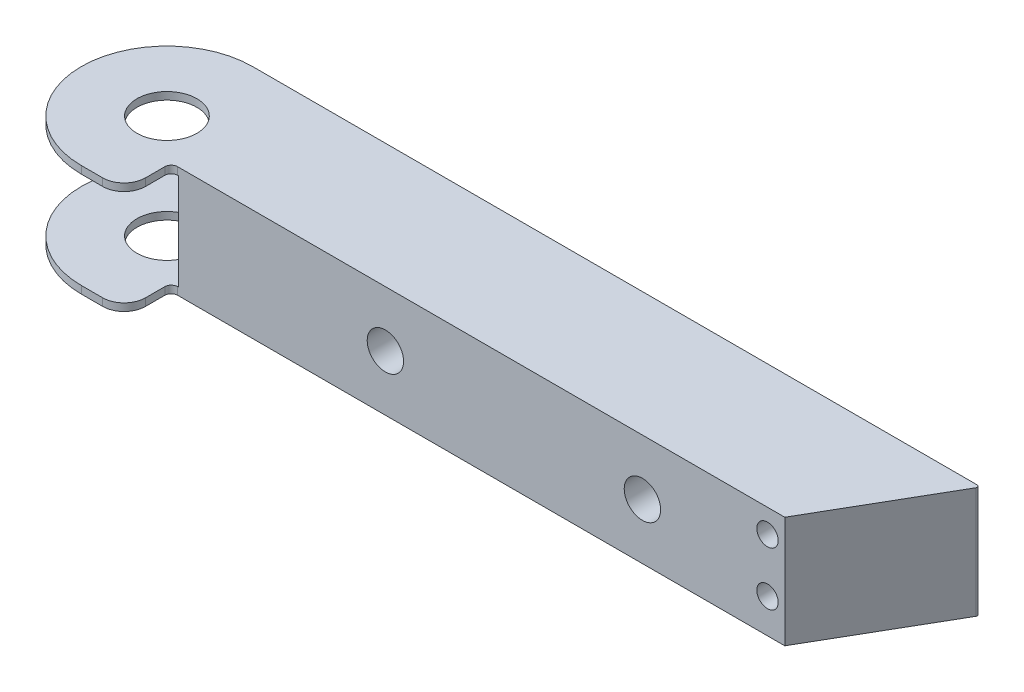
SolidWorks part; units mm, degrees
material "Nylon 6/10"
ref_plane "Front Plane" through (0, 0, 0) normal (0, 0, 1) x (1, 0, 0)
ref_plane "Top Plane" through (0, 0, 0) normal (0, 1, 0) x (1, 0, 0)
ref_plane "Right Plane" through (0, 0, 0) normal (1, 0, 0) x (0, 0, -1)
sketch "Sketch1" plane through (0, 0, 0) normal (0, 1, 0) x (1, 0, 0)
  line L0 (0, 0) -> (38, 0)
  line L1 (38, 0) -> (30, -8)
  line L2 (30, -8) -> (0, -8)
  line L3 (0, -8) -> (0, 0)
  dimension "D1" = 38
  dimension "D2" = 30
  dimension "D3" = 8
extrude "Boss-Extrude1" add sketch "Sketch1" along normal blind 5.5
sketch "Sketch3" plane through (0, 5.5, 0) normal (0, 1, 0) x (1, 0, 0)
  line L0 (2, 0) -> (2, -2) construction
  line L1 (38, 0) -> (0, 0) construction
  line L2 (2, -2) -> (0, -2) construction
  line L3 (0, 0) -> (0, -8) construction
  dimension "D1" = 2
  dimension "D2" = 2
sketch "Sketch4" plane through (0, 0, 8) normal (0, 0, 1) x (1, 0, 0)
  line L12 (0, 0.5) -> (6, 0.5)
  line L13 (0, 5.5) -> (0, 0) construction
  line L14 (6, 0.5) -> (6, 0)
  line L15 (0, 0) -> (30, 0) construction
  line L16 (6, 0) -> (38, 0)
  line L17 (38, 0) -> (38, 5.5)
  line L18 (38, 5.5) -> (6, 5.5)
  line L19 (0, 5.5) -> (30, 5.5) construction
  line L20 (6, 5.5) -> (6, 5)
  line L21 (6, 5) -> (0, 5)
  line L22 (0, 5) -> (0, 0.5)
  dimension "D1" = 6
  dimension "D2" = 6
  dimension "D3" = 0.5
  dimension "D4" = 0.5
extrude "Cut-Extrude1" cut sketch "Sketch4" against normal blind 3.5
fillet "Fillet2" radius 4 3 edges at (0, 0.25, 8) (0, 5.25, 8) (0, 2.75, 0)
sketch "Sketch13" plane through (0, 0, 0) normal (0, 0, -1) x (-1, 0, 0)
  line L0 (-38, 0) -> (-4, 0) construction
  line L3 (-4, 0) -> (-4, 5.5) construction
  circle A0 centre (-33.84, 4.25) radius 0.5
  circle A1 centre (-33.84, 1.75) radius 0.5
  dimension "D1" = 1
  dimension "D2" = 1
  dimension "D4" = 1.75
  dimension "D5" = 29.84
  dimension "D3" = 2.5
sketch "Sketch15" plane through (0, 0, 0) normal (0, 0, -1) x (-1, 0, 0)
  line L0 (-4, 2.75) -> (-28, 2.75) construction
  line L1 (-4, 0) -> (-4, 5.5) construction
  line L2 (-28, 2.75) -> (-28, 5.5) construction
  line L3 (-38, 5.5) -> (-4, 5.5) construction
  line L4 (-23, 2.75) -> (-23, 5.5) construction
  dimension "D1" = 5
  dimension "D2" = 19
sketch "Sketch19" plane through (0, 5.5, 0) normal (0, 1, 0) x (1, 0, 0)
  circle A0 centre (4, -4) radius 1.4
  point P0 (4, -4)
extrude "Cut-Extrude3" cut sketch "Sketch19" against normal blind 6.3
sketch "Sketch21" plane through (0, 0.5, 0) normal (0, 1, 0) x (1, 0, 0)
  circle A0 centre (4, -4) radius 2.4
  point P0 (4, -4)
extrude "Cut-Extrude4" cut sketch "Sketch21" along normal blind 4.5
sketch "Sketch22" plane through (0, 0, 4.5) normal (0, 0, 1) x (1, 0, 0)
  line L0 (6.3473, 5) -> (6, 5)
  line L1 (6, 5) -> (6, 5.5)
  line L2 (6, 5.5) -> (33.5, 5.5)
  line L3 (33.5, 5.5) -> (33.5, 0)
  line L4 (33.5, 0) -> (6, 0)
  line L5 (6, 0) -> (6, 0.5)
  line L6 (6, 0.5) -> (6.3473, 0.5)
  line L7 (6.3473, 0.5) -> (6.3473, 5)
  point P16 (0, 0)
extrude "Boss-Extrude3" add sketch "Sketch22" along normal blind 1.3
fillet "Fillet5" radius 0.3 2 edges at (6, 0.25, 5.8) (6, 5.25, 5.8)
fillet "Fillet6" radius 1 2 edges at (6, 0.25, 8) (6, 5.25, 8)
sketch "Sketch25" plane through (0, 5.5, 0) normal (0, 1, 0) x (1, 0, 0)
  line L0 (38, 0) -> (33.5, -4.5)
  line L1 (33.5, -4.5) -> (33.5, -5.8)
  line L2 (33.5, -5.8) -> (34.6462, -5.8)
  line L3 (34.6462, -5.8) -> (38, 0)
  line L4 (38, 0) -> (4, 0) construction
  dimension "D1" = 59.962
extrude "Boss-Extrude4" add sketch "Sketch25" against normal blind 5.5
extrude "Cut-Extrude5" cut sketch "Sketch13" against normal blind 6.5
fillet "Fillet7" radius 0.1 1 edges at (38, 2.75, 0)
ref_plane "Plane1" through (0, 5.5, 0) normal (0, 1, 0) x (1, 0, 0)
sketch "Sketch30" plane through (0, 5.5, 0) normal (0, 1, 0) x (1, 0, 0)
  line L0 (39.9507, 0.4511) -> (-1.7146, 0.4511)
  line L1 (-1.7146, 0.4511) -> (-1.7146, -8.528)
  line L2 (-1.7146, -8.528) -> (39.9507, -8.528)
  line L3 (39.9507, -8.528) -> (39.9507, 0.4511)
extrude "Cut-Extrude6" cut sketch "Sketch30" against normal blind 0.15
ref_plane "Plane2" through (0, 0, 0) normal (0, -1, 0) x (-1, 0, 0)
sketch "Sketch31" plane through (0, 0, 0) normal (0, -1, 0) x (-1, 0, 0)
  line L0 (1.8378, 0.4313) -> (1.8378, -8.4743)
  line L1 (1.8378, -8.4743) -> (-39.7571, -8.4743)
  line L2 (-39.7571, -8.4743) -> (-39.7571, 0.4313)
  line L3 (-39.7571, 0.4313) -> (1.8378, 0.4313)
extrude "Cut-Extrude7" cut sketch "Sketch31" against normal blind 0.15
sketch "Sketch32" plane through (0, 0, 0) normal (0, 0, -1) x (-1, 0, 0)
  line L0 (-4, 0.15) -> (-4, 5.35) construction
  point P0 (-16, 2.75)
  point P3 (-4, 2.75)
  point P4 (-28, 2.75)
  dimension "D1" = 12
  dimension "D2" = 24
hole_wizard "M1.6 Clearance Hole1" positions "Sketch35" profile "Sketch36" hole size "M1.6" standard "ANSI Metric" end condition through all
sketch "Sketch35" plane through (0, 0, 0) normal (0, 0, -1) x (-1, 0, 0)
  point P0 (-16, 2.75)
  point P3 (-28, 2.75)
sketch "Sketch36" plane through (16, 2.75, 0) normal (1, 0, 0) x (0, 1, 0)
  line L0 (0, 0) -> (0, 8)
  line L1 (0, 8) -> (0.85, 8)
  line L2 (0.85, 8) -> (0.85, 0)
  line L5 (0.85, 0) -> (0, 0)
  line L11 (0, -6.35) -> (0, 107.95) construction
  dimension "Thru Hole Dia." = 1.7
  dimension "Thru Hole Depth" = 8
sketch "Sketch37" plane through (0, 5, 0) normal (0, -1, 0) x (1, 0, 0)
  line L0 (4, -0.4422) -> (4, 8.4422)
  arc A0 (4, 8.4422) -> (4, -0.4422) centre (4, 4) ccw
extrude "Cut-Extrude8" cut sketch "Sketch37" along normal up to surface (4.5 mm away) up to face at (4.5736, 0.5, 5.7994)
